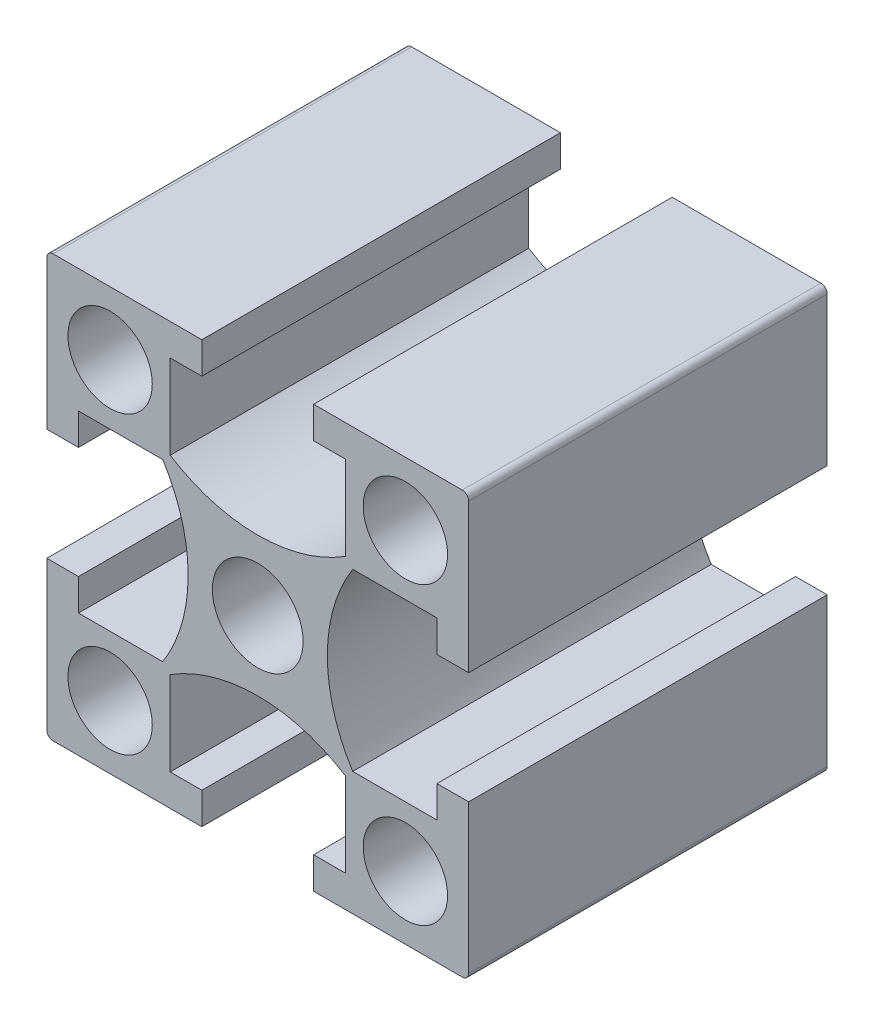
SolidWorks part; units mm, degrees
material "3.0255 (EN-AW 1350A)"
ref_plane "정면" through (0, 0, 0) normal (0, 0, 1) x (1, 0, 0)
ref_plane "윗면" through (0, 0, 0) normal (0, 1, 0) x (1, 0, 0)
ref_plane "우측면" through (0, 0, 0) normal (1, 0, 0) x (0, 0, -1)
sketch "스케치1" plane through (0, 0, 0) normal (0, 0, 1) x (1, 0, 0)
  line L0 (0, 32.0265) -> (0, -31.6588) construction
  line L1 (-10, 10) -> (-10, -10)
  line L2 (-10, 10) -> (10, 10)
  line L3 (-10, 2.65) -> (-8.5, 2.65)
  line L4 (13.6618, 0) -> (-11.6993, 0) construction
  line L5 (-8.5, 2.65) -> (-8.5, 4.15)
  line L6 (-8.5, 4.15) -> (-4.5032, 4.15)
  line L7 (-10, -2.65) -> (-8.5, -2.65)
  line L8 (-8.5, -2.65) -> (-8.5, -4.15)
  line L9 (-8.5, -4.15) -> (-4.5032, -4.15)
  line L10 (-10, -10) -> (10, -10)
  line L11 (10, 10) -> (10, -10)
  circle A0 centre (-7, 7) radius 2
  circle A1 centre (-7, -7) radius 2
  arc A2 (-4.5032, 4.15) -> (-4.5032, -4.15) centre (-11.0587, 0) cw
  circle A3 centre (0, 0) radius 2.15
  circle A4 centre (7, 7) radius 2
  circle A5 centre (7, -7) radius 2
  point P21 (-10, 0)
  point P23 (-3.3, 0)
  point P31 (0, -10)
  point P32 (0, 10)
  dimension "D3" = 4
  dimension "D9" = 6.7
  dimension "D10" = 4.3
  dimension "D11" = 7.7587
  dimension "D1" = 20
  dimension "D2" = 20
  dimension "D4" = 14
  dimension "D5" = 14
  dimension "D6" = 5.3
  dimension "D7" = 8.3
  dimension "D8" = 1.5
extrude "보스-돌출1" add sketch "스케치1" along normal blind 17 contours A0 | A4 | A3 | A5 | A1 | A2 L6 L5 L3 L1 L7 L8 L9 | L2 L11 L10 L1 region at (-6.6069, 0, 0) region at (-7, 7, 0) region at (-7, -7, 0) region at (0, 0, 0) region at (7, 7, 0) region at (7, -7, 0)
extrude "컷-돌출1" cut sketch "스케치1<3>" along normal up to next contours A2 L6 L5 L3 L1 L7 L8 L9 region at (-6.6069, 0, 0)
sketch "스케치1<3>" plane through (0, 0, 0) normal (0, 0, 1) x (1, 0, 0) same geometry as "스케치1"
pattern_circular "원형 패턴1" count 4 over 360 about axis through (0, 0, 17) along (0, 0, -1) of "컷-돌출1" reverse direction yes
fillet "필렛1" radius 0.3 4 edges at (10, -10, 8.5) (-10, -10, 8.5) (-10, 10, 8.5) (10, 10, 8.5)
sketch "스케치2" plane through (0, 0, 0) normal (1, 0, 0) x (0, 0, -1)
  line L0 (3.7612, 0) -> (-18.9549, 0) construction
  line L1 (-8.5, 34.3807) -> (-8.5, -14.9807) construction
  line L5 (0, 9.7) -> (-17, 9.7) construction
  line L6 (0, 9.7) -> (-17, 9.7) construction
  circle A0 centre (-8.5, 0) radius 2.5
  point P6 (-8.5, 9.7)
  dimension "D1" = 5
extrude "컷-돌출2" cut sketch "스케치2" against normal through all both and the other way through all contours A0
